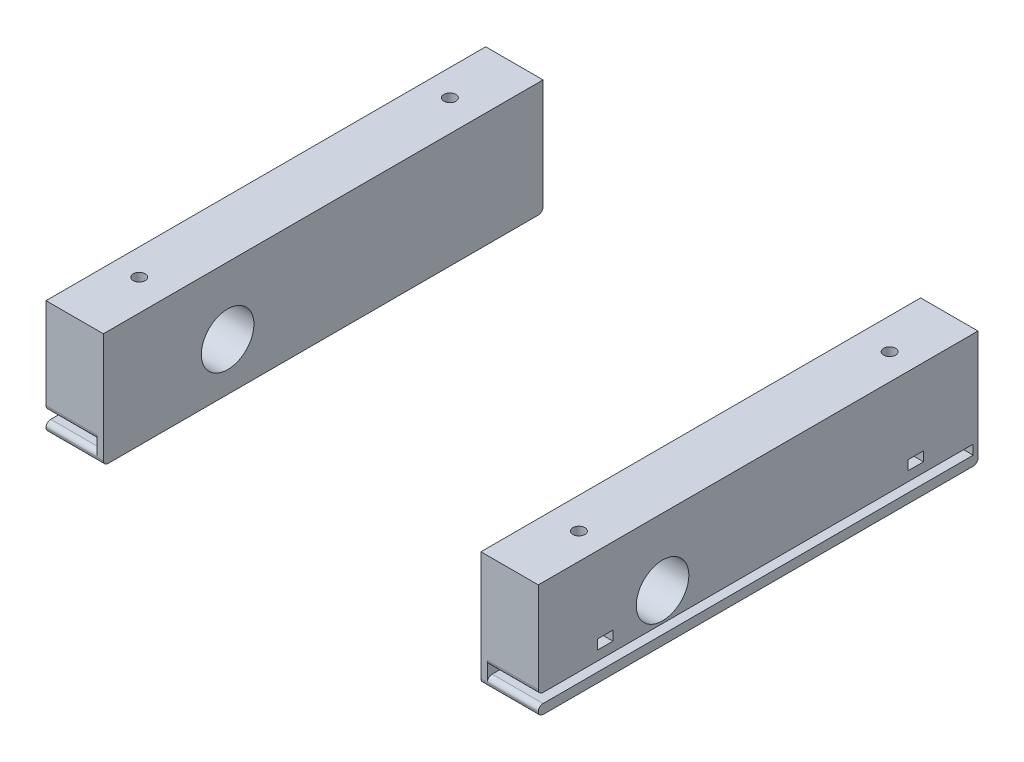
SolidWorks part; units mm, degrees
ref_plane "Front Plane" through (0, 0, 0) normal (0, 0, 1) x (1, 0, 0)
ref_plane "Top Plane" through (0, 0, 0) normal (0, 1, 0) x (1, 0, 0)
ref_plane "Right Plane" through (0, 0, 0) normal (1, 0, 0) x (0, 0, -1)
sketch "Sketch3" plane through (0, 15.4347, 0) normal (0, -1, 0) x (1, 0, 0)
  line L1 (17.3447, 34.0649) -> (17.3447, -45.9351)
  line L4 (23.3447, -38.9351) -> (23.3447, 26.0649) construction
  line L7 (29.3447, 34.0649) -> (29.3447, -45.9351)
  line L8 (17.3447, 34.0649) -> (17.3447, 40.0649)
  line L9 (17.3447, 40.0649) -> (29.3447, 40.0649)
  line L10 (29.3447, 40.0649) -> (29.3447, 34.0649)
  line L11 (17.3447, -45.9351) -> (17.3447, -51.9351)
  line L12 (17.3447, -51.9351) -> (29.3447, -51.9351)
  line L13 (29.3447, -51.9351) -> (29.3447, -45.9351)
  circle A9 centre (23.8447, -38.9351) radius 1.25
  circle A11 centre (23.8447, 26.0649) radius 1.25
  dimension "D3" = 2.5
  dimension "D4" = 2.5
  dimension "D1" = 6
  dimension "D2" = 80
extrude "Boss-Extrude1" add sketch "Sketch3" along normal blind 24
ref_plane "Plane1" through (-22.1553, 0, 0) normal (-1, 0, 0) x (0, 0, 1)
ref_plane "Plane2" through (0, 0, 40.0649) normal (0, 0, 1) x (1, 0, 0)
sketch "Sketch6" plane through (0, 0, 40.0649) normal (0, 0, 1) x (1, 0, 0)
  line L1 (29.3447, -6.5653) -> (18.6907, -6.5653)
  line L14 (29.3447, -4.5653) -> (18.6907, -4.5653)
  line L22 (29.3447, -6.5653) -> (29.3447, -4.5653)
  line L24 (18.6907, -6.5653) -> (18.6907, -4.5653)
  line L25 (29.3447, 15.4347) -> (17.3447, 15.4347) construction
  dimension "D1" = 20
extrude "Cut-Extrude1" cut sketch "Sketch6" against normal blind 91
sketch "Sketch7" plane through (29.3447, 0, 0) normal (1, 0, 0) x (0, 0, -1)
  line L1 (98.9351, 15.4347) -> (-125.0649, 15.4347) construction
  line L3 (51.9351, 15.4347) -> (-40.0649, 15.4347) construction
  line L5 (-27.6649, -0.5653) -> (-24.4649, -0.5653)
  line L6 (-27.6649, -0.5653) -> (-27.6649, -2.5653)
  line L7 (-27.6649, -2.5653) -> (-24.4649, -2.5653)
  line L8 (-24.4649, -0.5653) -> (-24.4649, -2.5653)
  line L9 (37.3351, -0.5653) -> (40.5351, -0.5653)
  line L10 (37.3351, -0.5653) -> (37.3351, -2.5653)
  line L11 (37.3351, -2.5653) -> (40.5351, -2.5653)
  line L12 (40.5351, -0.5653) -> (40.5351, -2.5653)
  dimension "D1" = 16
  dimension "D2" = 16
extrude "Cut-Extrude3" cut sketch "Sketch7" against normal up to surface (10.654 mm away) up to face at (18.6907, -5.5653, -5.4351)
fillet "Fillet1" radius 1 4 edges at (23.3447, -8.5653, 40.0649) (23.3447, -8.5653, -51.9351) (24.0177, -4.5653, 40.0649) (24.0177, -6.5653, 40.0649)
sketch "Sketch8" plane through (29.3447, 0, 0) normal (1, 0, 0) x (0, 0, -1)
  line L0 (-24.4649, -0.5653) -> (-27.6649, -0.5653) construction
  line L1 (-26.0649, -0.5653) -> (-26.0649, 12.096) construction
  line L2 (51.9351, 15.4347) -> (-40.0649, 15.4347) construction
  circle A0 centre (-14.0649, 1.4347) radius 5.5
  dimension "D1" = 11
  dimension "D2" = 12
  dimension "D3" = 14
extrude "Cut-Extrude4" cut sketch "Sketch8" against normal up to surface (12 mm away) up to face at (17.3447, -0.301, -5.9351)
mirror "Mirror4" about plane through (-22.1553, 0, 0) normal (-1, 0, 0) of bodies 109 101
